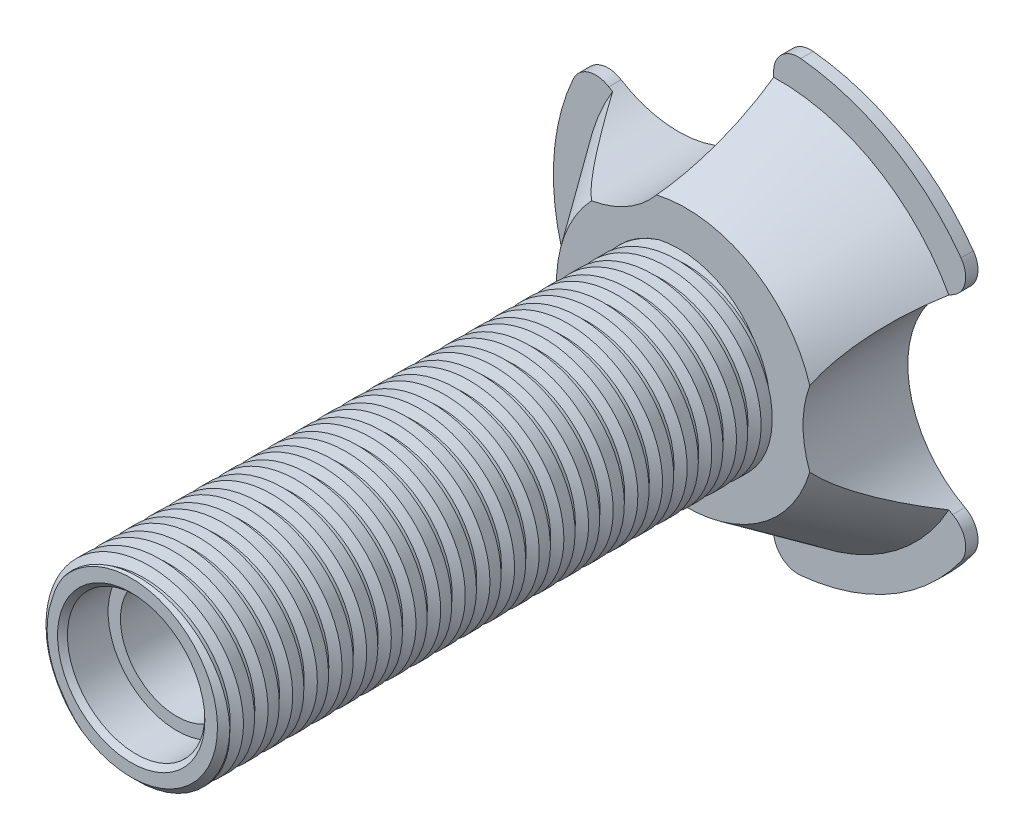
SolidWorks part; units mm, degrees
ref_plane "Спереди" through (0, 0, 0) normal (0, 0, 1) x (1, 0, 0)
ref_plane "Сверху" through (0, 0, 0) normal (0, 1, 0) x (1, 0, 0)
ref_plane "Справа" through (0, 0, 0) normal (1, 0, 0) x (0, 0, -1)
sketch "Эскиз1" plane through (0, 0, 0) normal (0, 0, 1) x (1, 0, 0)
  circle A0 centre (0, 0) radius 15
  dimension "D1" = 30
extrude "Бобышка-Вытянуть1" add sketch "Эскиз1" along normal blind 90
sketch "Эскиз2" plane through (0, 0, 0) normal (0, 0, -1) x (-1, 0, 0)
  circle A2 centre (0, 0) radius 21
  dimension "D1" = 42
extrude "Бобышка-Вытянуть2" add sketch "Эскиз2" along normal blind 15 draft 35 draft outward yes
sketch "Эскиз6" plane through (0, 0, -15) normal (0, 0, -1) x (-1, 0, 0)
  circle A0 centre (0, 0) radius 31.5031 construction
  circle A2 centre (0, 0) radius 36.5031
  dimension "D1" = 5
extrude "Бобышка-Вытянуть3" add sketch "Эскиз6" along normal blind 2
sketch "Эскиз7" plane through (0, 0, -17) normal (0, 0, -1) x (-1, 0, 0)
  circle A1 centre (0, 0) radius 31.5031 construction
  circle A2 centre (0, 0) radius 31.5031 construction
  circle A3 centre (-36.5031, 0) radius 17.5
  circle A4 centre (18.2516, 31.6126) radius 17.5
  circle A5 centre (18.2516, -31.6126) radius 17.5
  circle A6 centre (0, 0) radius 36.5031 construction
  point P2 (-35, 0)
  point P12 (0, 0)
  point P13 (-35, 0)
  point P14 (0, 0)
  point P15 (27.2869, -16.4045)
  point P16 (0, 0)
  dimension "D1" = 35
  dimension "D2" = 3
extrude "Вырез-Вытянуть1" cut sketch "Эскиз7" against normal through all
fillet "Скругление1" radius 4 6 edges at (32.3083, -16.9898, -16) (32.3083, 16.9898, -16) (-1.4405, -36.4747, -16) (-30.8677, -19.4849, -16) (-30.8677, 19.4849, -16) (-1.4405, 36.4747, -16)
chamfer "Фаска1" distance 1 angle 45 1 edges at (15, 0, 90)
thread "Резьба1" pitch 2.5 start angle 0, offset 10, length 0, pitch 4, diameter 30
ref_plane "Плоскость1" through (-15, 0, 99) normal (0, -1, 0) x (-1, 0, 0)
sketch "Профиль резьбы1" plane through (-15, 0, 99) normal (0, -1, 0) x (-1, 0, 0)
  line L0 (0, 0) -> (0, 2.5) construction
  line L11 (0, 0) -> (0, 2.1875)
  line L12 (0, 2.1875) -> (-1.3532, 1.4062)
  line L13 (-1.3532, 1.4062) -> (-1.3532, 0.7812)
  line L15 (-1.3532, 0.7812) -> (0, 0)
  line L17 (-1.3532, 1.0937) -> (0, 1.0937) construction
  point P2 (0, 0)
  dimension "Pitch" = 2.5
  dimension "Profile_Angle" = 60
  dimension "Profile_Land" = 0.625
  dimension "Profile_Height" = 1.3532
sketch "Эскиз8" plane through (0, 0, 90) normal (0, 0, 1) x (1, 0, 0)
  circle A0 centre (0, 0) radius 11.15
  dimension "D1" = 22.3
extrude "Вырез-Вытянуть2" cut sketch "Эскиз8" against normal blind 7.4
sketch "Эскиз9" plane through (0, 0, -17) normal (0, 0, -1) x (-1, 0, 0)
  circle A0 centre (0, 0) radius 11.15
  dimension "D1" = 22.3
extrude "Вырез-Вытянуть3" cut sketch "Эскиз9" against normal blind 7.4
chamfer "Фаска2" distance 0.8 angle 45 2 edges at (-11.15, 0, -17) (11.15, 0, 90)
sketch "Эскиз10" plane through (0, 0, -9.6) normal (0, 0, -1) x (-1, 0, 0)
  circle A2 centre (0, 0) radius 9.15
  circle A3 centre (0, 0) radius 9.15
  dimension "D1" = 2
extrude "Вырез-Вытянуть4" cut sketch "Эскиз10" against normal through all
